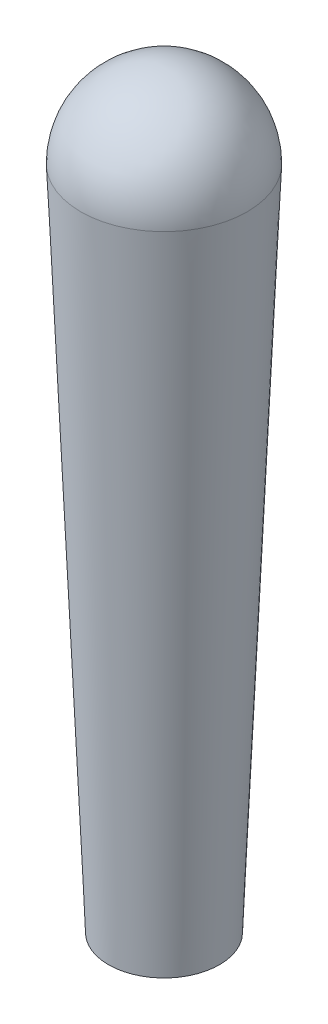
SolidWorks part; units mm, degrees
ref_plane "Front" through (0, 0, 0) normal (0, 0, 1) x (1, 0, 0)
ref_plane "Top" through (0, 0, 0) normal (0, 1, 0) x (1, 0, 0)
ref_plane "Right" through (0, 0, 0) normal (1, 0, 0) x (0, 0, -1)
sketch "Sketch1" plane through (0, 0, 0) normal (0, 1, 0) x (1, 0, 0)
  line L1 (-1, 0) -> (1, 0) construction
  circle A0 centre (0, 0) radius 1
  dimension "D1" = 2
ref_axis "Axis1" through (-1, 0, 0) along (1, 0, 0)
ref_plane "Plane1" through (0, 12, 0) normal (0, 1, 0) x (1, 0, 0)
sketch "Sketch2" plane through (0, 12, 0) normal (0, 1, 0) x (1, 0, 0)
  circle A0 centre (0, 0) radius 1.5
  dimension "D1" = 3
loft "Loft1" add profiles "Sketch1", "Sketch2" connector at (0, 0, 1) connector at (0, 12, 1.5)
sketch "Sketch3" plane through (0, 0, 0) normal (0, 0, 1) x (1, 0, 0)
  line L0 (0, 0) -> (0, 14.1618) construction
  line L1 (0, 12) -> (1.5, 12)
  line L2 (0, 13.5) -> (0, 12)
  arc A0 (1.5, 12) -> (0, 13.5) centre (0, 12) ccw
  dimension "D1" = 12
  dimension "D2" = 1.5
revolve "Revolve1" add sketch "Sketch3" angle 360 about L0
